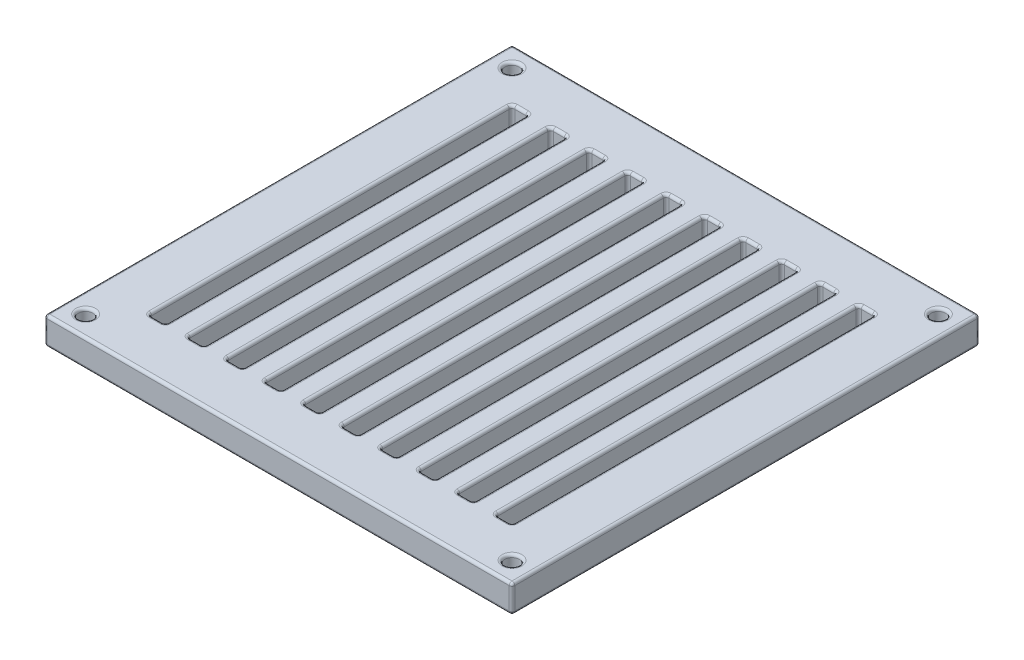
SolidWorks part; units mm, degrees
ref_plane "Front Plane" through (0, 0, 0) normal (0, 0, 1) x (1, 0, 0)
ref_plane "Top Plane" through (0, 0, 0) normal (0, 1, 0) x (1, 0, 0)
ref_plane "Right Plane" through (0, 0, 0) normal (1, 0, 0) x (0, 0, -1)
sketch "Sketch2" plane through (0, 0, 0) normal (0, 1, 0) x (1, 0, 0)
  line L1 (0, 0) -> (85, 0)
  line L2 (0, 0) -> (0, 85)
  line L3 (0, 85) -> (85, 85)
  line L4 (85, 0) -> (85, 85)
  dimension "D1" = 85
  dimension "D2" = 85
extrude "Boss-Extrude1" add sketch "Sketch2" along normal blind 5
sketch "Sketch3" plane through (0, 5, 0) normal (0, 1, 0) x (1, 0, 0)
  line L0 (0, 85) -> (0, 0) construction
  line L1 (0, 0) -> (85, 0) construction
  circle A0 centre (3.75, 3.75) radius 1.3
  dimension "D1" = 2.6
  dimension "D2" = 3.75
  dimension "D3" = 3.75
extrude "Cut-Extrude1" cut sketch "Sketch3" against normal through all
pattern_linear "LPattern1" count 2 spacing 77.5 along (1, 0, 0) count 2 spacing 77.5 along (0, 0, -1) of "Cut-Extrude1"
sketch "Sketch4" plane through (0, 5, 0) normal (0, 1, 0) x (1, 0, 0)
  line L0 (0, 85) -> (0, 0) construction
  line L1 (9.5, 75.5) -> (12.5, 75.5)
  line L2 (9.5, 75.5) -> (9.5, 9.5)
  line L3 (9.5, 9.5) -> (12.5, 9.5)
  line L4 (12.5, 75.5) -> (12.5, 9.5)
  line L5 (85, 85) -> (0, 85) construction
  line L6 (0, 0) -> (85, 0) construction
  dimension "D1" = 3
  dimension "D2" = 9.5
  dimension "D3" = 9.5
  dimension "D4" = 9.5
extrude "Cut-Extrude2" cut sketch "Sketch4" against normal through all
fillet "Fillet1" radius 0.5 12 edges at (11, 0, -9.5) (11, 5, -9.5) (9.5, 0, -42.5) (9.5, 2.5, -9.5) (9.5, 5, -42.5) (11, 0, -75.5) (9.5, 2.5, -75.5) (11, 5, -75.5) (12.5, 2.5, -9.5) (12.5, 0, -42.5) (12.5, 2.5, -75.5) (12.5, 5, -42.5)
pattern_linear "LPattern2" count 10 spacing 7 along (1, 0, 0) of "Fillet1", "Cut-Extrude2"
fillet "Fillet2" radius 0.5 16 edges at (81.25, 0, -79.95) (3.75, 0, -79.95) (42.5, 0, 0) (85, 0, -42.5) (42.5, 0, -85) (0, 0, -42.5) (3.75, 0, -2.45) (81.25, 0, -2.45) (81.25, 5, -79.95) (3.75, 5, -79.95) (42.5, 5, -85) (85, 5, -42.5) (42.5, 5, 0) (0, 5, -42.5) (3.75, 5, -2.45) (81.25, 5, -2.45)
fillet "Fillet3" radius 0.5 12 edges at (84.8536, 4.8536, -0.1464) (84.8536, 0.1464, -0.1464) (84.8536, 4.8536, -84.8536) (84.8536, 0.1464, -84.8536) (0.1464, 4.8536, -0.1464) (0.1464, 0.1464, -0.1464) (0.1464, 4.8536, -84.8536) (0.1464, 0.1464, -84.8536) (85, 2.5, 0) (85, 2.5, -85) (0, 2.5, 0) (0, 2.5, -85)
